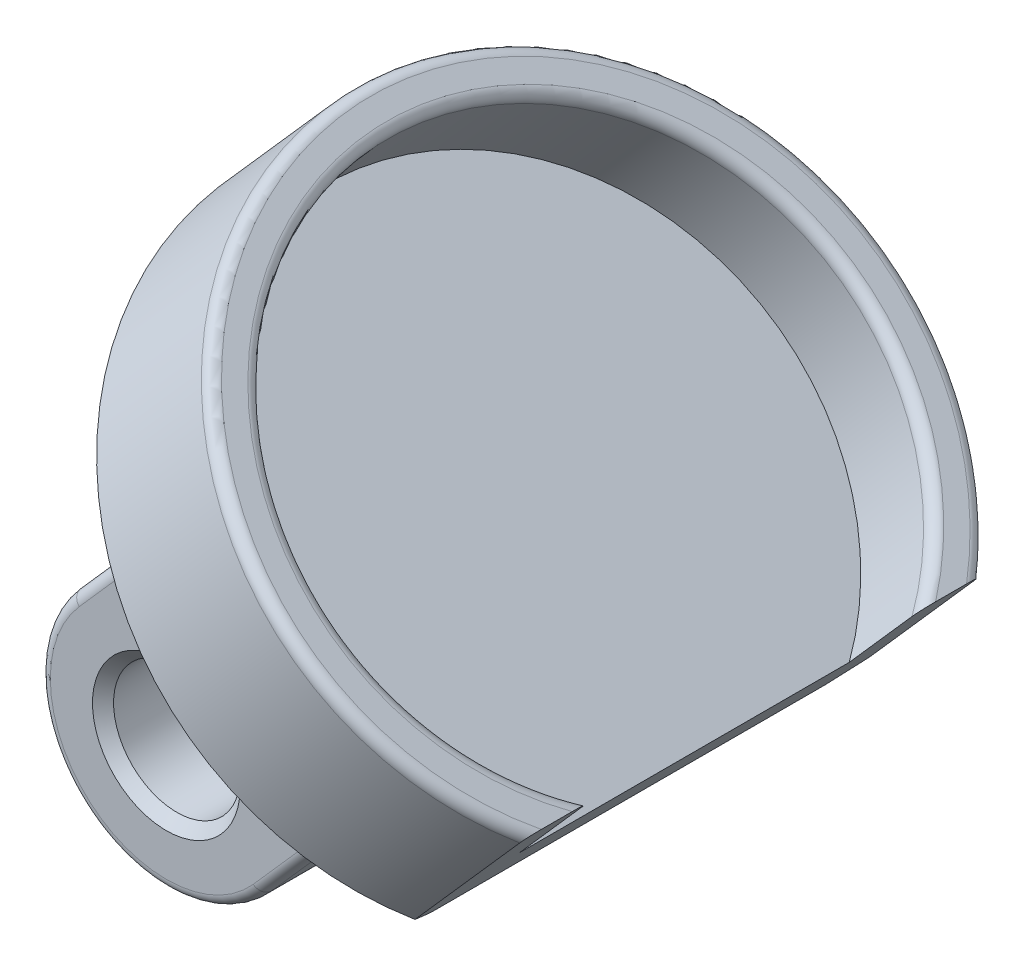
SolidWorks part; units mm, degrees
ref_plane "Front Plane" through (0, 0, 0) normal (0, 0, 1) x (1, 0, 0)
ref_plane "Top Plane" through (0, 0, 0) normal (0, 1, 0) x (1, 0, 0)
ref_plane "Right Plane" through (0, 0, 0) normal (1, 0, 0) x (0, 0, -1)
sketch "Sketch1" plane through (0, 0, 0) normal (0, 0, 1) x (1, 0, 0)
  line L1 (2.9256, 48.9181) -> (97.0713, 14.6519)
  line L2 (97.0713, 14.6519) -> (114.1723, 61.6365) construction
  line L3 (2.9256, 48.9181) -> (16.6344, 86.5828) construction
  line L4 (64.2, 56.8) -> (64.2, 145) construction
  line L5 (17.2835, 64.9758) -> (54.2, 106.8)
  line L6 (74.2, 121.8) -> (101.5245, 50.2773)
  line L7 (40.7, 148) -> (40.7, 52.5253) construction
  line L8 (87.7, 148) -> (87.7, 56.8) construction
  arc A1 (97.0713, 14.6519) -> (108.8436, 11.9213) centre (114.1723, 61.6365) ccw
  circle A2 centre (17.2835, 64.9758) radius 3
  circle A3 centre (101.5245, 50.2773) radius 3
  circle A8 centre (74.2, 121.8) radius 3
  circle A9 centre (54.2, 106.8) radius 3
  spline S1 degree 3 poles (108.8436, 11.9213) (110.0019, 11.7972) (111.159, 11.6604) (114.5227, 11.2279) (116.7249, 10.9021) (123.3121, 9.8294) (127.6782, 8.9871) (140.7169, 6.3137) (149.3307, 4.3374) (166.474, 1.206) (175.0008, 0.0515) (187.7816, -0.2014) (192.0406, -0.0398) (200.5758, 0.9156) (204.8521, 1.7093) (209.1515, 2.8921) knots 0.514918 0.514918 0.514918 0.514918 0.53125 0.53125 0.5625 0.5625 0.625 0.625 0.75 0.75 0.875 0.875 0.9375 0.9375 1 1 1 1
  point P0 (64.2, 56.8)
  point P18 (17.2835, 64.9758)
  point P19 (101.5245, 50.2773)
  point P26 (74.2, 121.8)
  point P27 (54.2, 106.8)
  point P31 (87.8622, 86.0387)
  point P32 (35.7418, 85.8879)
  dimension "D11" = 6
  dimension "D12" = 6
  dimension "D15" = 46.9165
  dimension "D17" = 6
  dimension "D18" = 6
  dimension "D3" = 20
  dimension "D4" = 35
  dimension "D5" = 8
  dimension "D6" = 10
  dimension "D7" = 8
  dimension "D8" = 10
  dimension "D9" = 65
  dimension "D10" = 50
  dimension "D13" = 37.3245
  dimension "D14" = 6.5227
  dimension "D16" = 8.1758
sketch "Sketch2" plane through (0, 0, 0) normal (0, 0, 1) x (1, 0, 0)
  line L0 (30.5124, 70.8965) -> (21.7819, 61.0053)
  line L1 (30.5124, 70.8965) -> (21.5157, 78.8375)
  line L3 (21.5157, 78.8375) -> (12.7852, 68.9463)
  line L6 (17.2835, 64.9758) -> (54.2, 106.8) construction
  circle A1 centre (17.2835, 64.9758) radius 3
  arc A2 (12.7852, 68.9463) -> (21.7819, 61.0053) centre (17.2835, 64.9758) ccw
  point P4 (21.6488, 69.9214)
  dimension "D1" = 6
  dimension "D2" = 3
  dimension "D3" = 13.193
extrude "Boss-Extrude1" add sketch "Sketch2" along normal blind 7 and the other way blind 7 contours A1 | L1 L3 A2 L0
sketch "Sketch3" plane through (48.5357, 54.988, 0) normal (0.6618, 0.7497, 0) x (0.7497, -0.6618, 0)
  circle A0 centre (-30.0399, 0) radius 14.7
  dimension "D1" = 29.4
extrude "Boss-Extrude2" add sketch "Sketch3" along normal blind 2 and the other way blind 2
sketch "Sketch4" plane through (49.8592, 56.4875, 0) normal (0.6618, 0.7497, 0) x (0.7497, -0.6618, 0)
  circle A0 centre (-30.0399, 0) radius 14.7
  circle A1 centre (-30.0399, 0) radius 12.7
  dimension "D1" = 25.4
  dimension "D2" = 2
extrude "Boss-Extrude3" add sketch "Sketch4" along normal blind 5
fillet "Fillet2" radius 0.5 2 edges at (21.1248, 88.5193, 0) (19.6253, 89.8428, 0)
fillet "Fillet4" radius 0.5 6 edges at (25.4854, 65.2012, -7) (13.313, 60.4775, -7) (16.4887, 73.1422, -7) (25.4854, 65.2012, 7) (13.313, 60.4775, 7) (16.4887, 73.1422, 7)
chamfer "Chamfer1" distance 0.5 angle 45 2 edges at (20.2835, 64.9758, 7) (20.2835, 64.9758, -7)
chamfer "Chamfer2" distance 1 angle 45 9 edges at (20.302, 77.2411, 6.8536) (20.1922, 77.338, 0) (20.302, 77.2411, -6.8536) (24.6905, 73.3675, -7) (29.0791, 69.4939, -6.8536) (29.1889, 69.397, 0) (29.0791, 69.4939, 6.8536) (24.6905, 73.3675, 7) (13.6696, 83.0953, 0)
sketch "Sketch5" plane through (53.1679, 60.2361, 0) normal (0.6618, 0.7497, 0) x (0.7497, -0.6618, 0)
  line L0 (-30.0399, 0) -> (-7.5278, 0) construction
  line L1 (-10.0399, 12.5) -> (-10.0399, -12.5)
  line L2 (-10.0399, 12.5) -> (-20.0399, 12.5)
  line L3 (-10.0399, -12.5) -> (-20.0399, -12.5)
  line L4 (-20.0399, 12.5) -> (-20.0399, -12.5)
  dimension "D2" = 25
  dimension "D3" = 10
  dimension "D4" = 10
extrude "Cut-Extrude1" cut sketch "Sketch5" against normal through all
